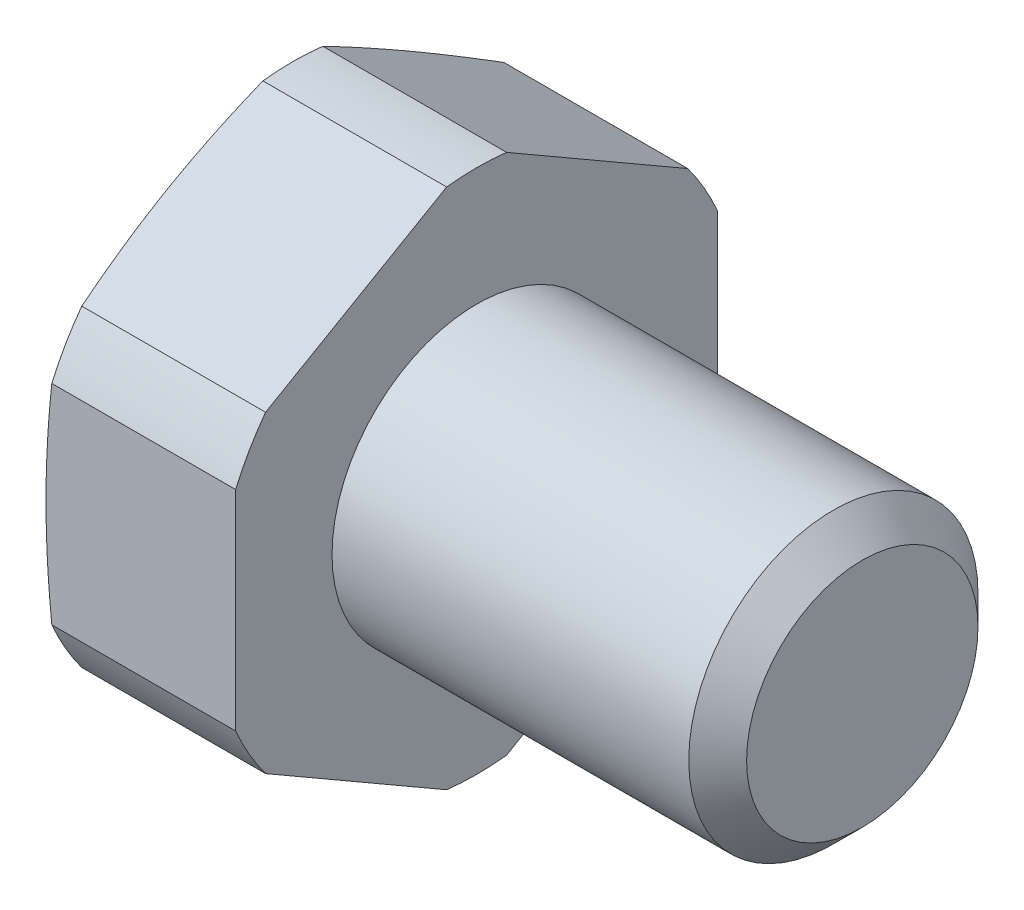
SolidWorks part; units mm, degrees
material "AISI 1020"
ref_plane "Спереди" through (0, 0, 0) normal (0, 0, 1) x (1, 0, 0)
ref_plane "Сверху" through (0, 0, 0) normal (0, 1, 0) x (1, 0, 0)
ref_plane "Справа" through (0, 0, 0) normal (1, 0, 0) x (0, 0, -1)
sketch "Эскиз1" plane through (0, 0, 0) normal (0, 0, 1) x (1, 0, 0)
  line L0 (-1000, 0) -> (49000, 0) construction
  line L1 (-4, 0) -> (-4, 4.75)
  line L2 (-4, 4.75) -> (-3.8124, 5.45)
  line L3 (-3.8124, 5.45) -> (0, 5.45)
  line L4 (0, 5.45) -> (0, 3)
  line L5 (0, 3) -> (7.4, 3)
  line L6 (8, 2.4) -> (8, 0)
  line L7 (8, 3) -> (8.5, 3.866) construction
  line L8 (8.5, 3.866) -> (9, 3) construction
  line L9 (9, 3) -> (8, 3) construction
  line L10 (8.5, 3.866) -> (8.5, 3) construction
  line L11 (8.5, 3.866) -> (0.5, 3.866) construction
  line L12 (7.4, 3) -> (8, 2.4)
  line L13 (8, 3) -> (7.7, 2.7) construction
  line L14 (-4, 4.75) -> (-14, 4.75) construction
  line L15 (-4, 0) -> (8, 0)
  dimension "D1" = 0.6
  dimension "D2" = 15
revolve "Повернуть1" add sketch "Эскиз1" angle 360 about L0
cosmetic thread "Условное изображение резьбы1" parameters "D1"=8, "D2"=4.2679
sketch "Эскиз2" plane through (-4, 0, 0) normal (-1, 0, 0) x (0, 0, 1)
  line L1 (0, 5.7735) -> (-5, 2.8868)
  line L2 (-5, 2.8868) -> (-5, -2.8868)
  line L3 (-5, -2.8868) -> (0, -5.7735)
  line L4 (0, -5.7735) -> (5, -2.8868)
  line L5 (5, -2.8868) -> (5, 2.8868)
  line L6 (5, 2.8868) -> (0, 5.7735)
  circle A0 centre (0, 0) radius 5 construction
  dimension "D1" = 10
extrude "Вырез-Вытянуть1" cut sketch "Эскиз2" against normal up to surface (12 mm away) flip side to cut up to face at (8, 0, 2.4)
equation "\"D1@Эскиз1\"=\"_d_@Эскиз1\"/10"
equation "\"D@Эскиз1\"=\"S_@Эскиз1\"*0.95"
equation "\"D1@Эскиз2\"=\"S_@Эскиз1\""
equation "\"D1@Условное изображение резьбы1\"=\"b_@Эскиз1\""
equation "\"D2@Условное изображение резьбы1\"=\"_d_@Эскиз1\"-\"dr@Эскиз1\"*2"
